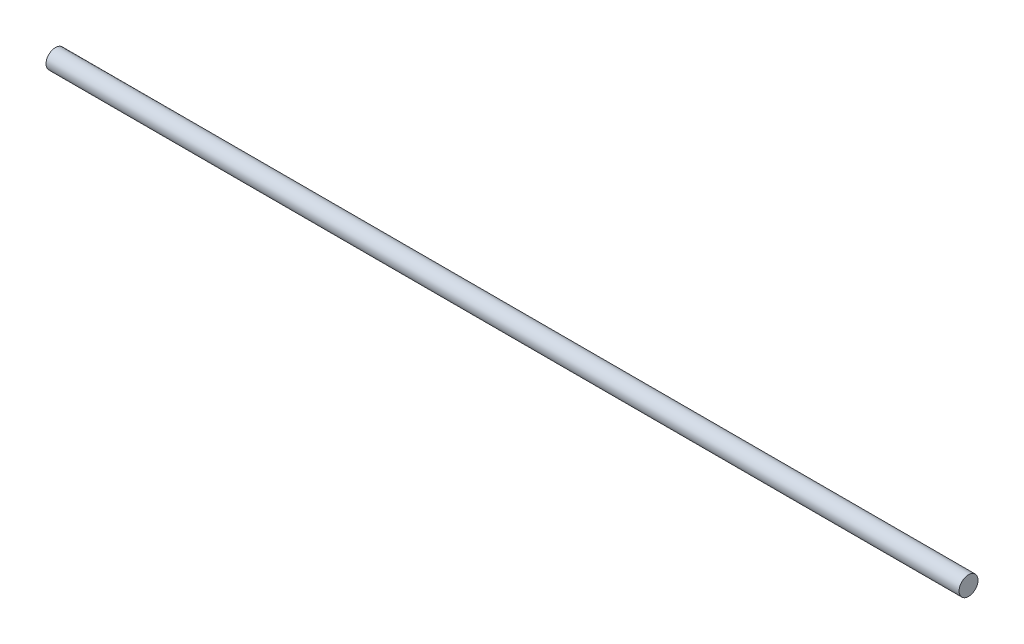
SolidWorks part; units mm, degrees
ref_plane "Front Plane" through (0, 0, 0) normal (0, 0, 1) x (1, 0, 0)
ref_plane "Top Plane" through (0, 0, 0) normal (0, 1, 0) x (1, 0, 0)
ref_plane "Right Plane" through (0, 0, 0) normal (1, 0, 0) x (0, 0, -1)
sketch "Sketch1" plane through (0, 0, 0) normal (1, 0, 0) x (0, 0, -1)
  circle A0 centre (0, 0) radius 2.5
  dimension "D1" = 5
extrude "Boss-Extrude1" add sketch "Sketch1" along normal mid plane 241.3
ref_axis "Idler Axis" through (-132.715, 0, 0) along (1, 0, 0)
